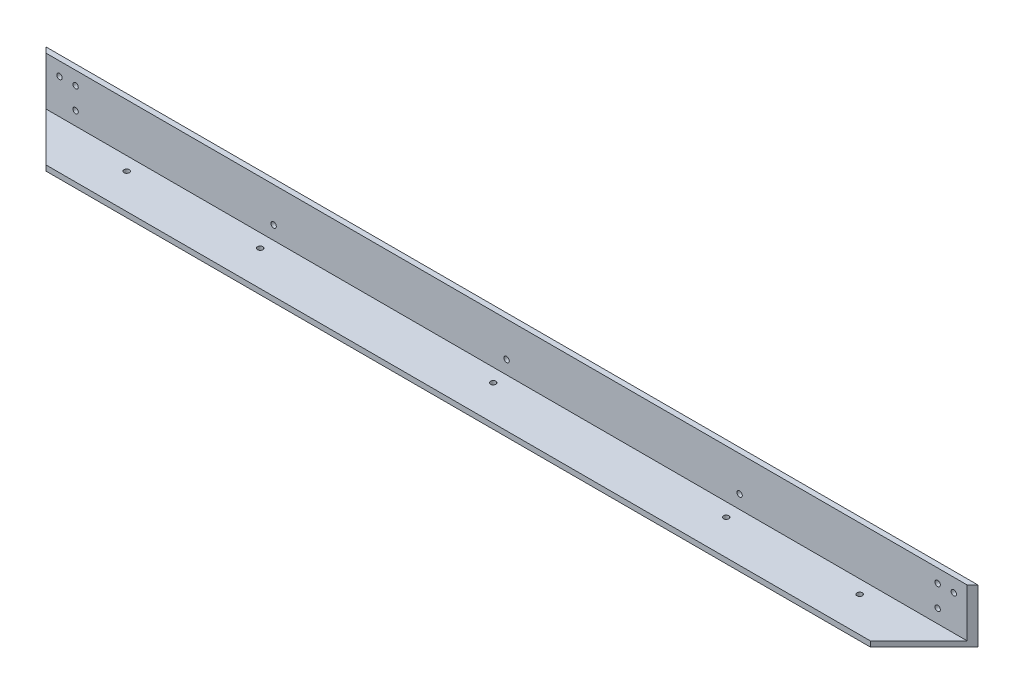
SolidWorks part; units mm, degrees
ref_plane "Front Plane" through (0, 0, 0) normal (0, 0, 1) x (1, 0, 0)
ref_plane "Top Plane" through (0, 0, 0) normal (0, 1, 0) x (1, 0, 0)
ref_plane "Right Plane" through (0, 0, 0) normal (1, 0, 0) x (0, 0, -1)
sketch "Sketch1" plane through (0, 0, 0) normal (1, 0, 0) x (0, 0, -1)
  line L0 (0, 0) -> (-31.75, 0)
  line L1 (-31.75, 0) -> (-31.75, 3.175)
  line L2 (-31.75, 3.175) -> (-3.175, 3.175)
  line L3 (-3.175, 3.175) -> (-3.175, 31.75)
  line L4 (-3.175, 31.75) -> (0, 31.75)
  line L5 (0, 31.75) -> (0, 0)
  dimension "LHeight" = 31.75
  dimension "LWidth" = 31.75
  dimension "LMaterialThickness" = 3.175
  dimension "D1" = 28.575
  dimension "D2" = 28.575
  dimension "D3" = 3.175
extrude "Boss-Extrude1" add sketch "Sketch1" along normal blind 550
chamfer "Chamfer6" distance 31.75 angle 45 1 edges at (550, 1.5875, 31.75)
chamfer "Chamfer7" distance 31.75 angle 45 1 edges at (0, 1.5875, 31.75)
sketch "TopHoles-Sketch3" plane through (0, 3.175, 0) normal (0, 1, 0) x (1, 0, 0)
  line L3 (550, 0) -> (0, 0) construction
  circle A9 centre (491.2625, -11.1125) radius 1.5875
  circle A10 centre (58.7375, -11.1125) radius 1.5875
  circle A13 centre (275, -11.1125) radius 1.5875
  circle A14 centre (137.5, -11.1125) radius 1.5875
  circle A15 centre (412.5, -11.1125) radius 1.5875
  point P8 (0, 0)
  point P9 (0, 0)
  point P11 (0, 0)
  point P12 (0, 0)
  point P20 (0, 0)
  point P21 (-1.5296, -23.0572)
  dimension "D8" = 137.5
  dimension "D10" = 137.5
  dimension "D5" = 3.175
  dimension "D11" = 137.5
  dimension "D2" = 11.1125
  dimension "D3" = 58.7375
  dimension "D4" = 58.7375
extrude "TopHoles-Cut-Extrude2" cut sketch "TopHoles-Sketch3" against normal through all
sketch "LeftHoles-Sketch4" plane through (0, 0, 3.175) normal (0, 0, 1) x (1, 0, 0)
  line L1 (550, 0) -> (0, 0) construction
  line L3 (550, 31.75) -> (0, 31.75) construction
  line L4 (0, 0) -> (0, 31.75) construction
  line L5 (550, 0) -> (550, 31.75) construction
  circle A1 centre (11.1125, 23.8125) radius 1.5875
  circle A3 centre (529.3625, 23.8125) radius 1.5875
  circle A4 centre (20.6375, 23.8125) radius 1.5875
  circle A5 centre (538.8875, 23.8125) radius 1.5875
  circle A7 centre (20.6375, 11.1125) radius 1.5875
  circle A8 centre (529.3625, 11.1125) radius 1.5875
  circle A10 centre (137.5, 11.1125) radius 1.5875
  circle A11 centre (275, 11.1125) radius 1.5875
  circle A12 centre (412.5, 11.1125) radius 1.5875
  dimension "D2" = 3.175
  dimension "D4" = 7.9375
  dimension "D1" = 11.1125
  dimension "D6" = 20.6375
  dimension "D3" = 11.1125
  dimension "D5" = 20.6375
  dimension "D8" = 137.5
  dimension "D9" = 137.5
  dimension "D10" = 137.5
  dimension "D7" = 11.1125
extrude "LeftHoles-Cut-Extrude3" cut sketch "LeftHoles-Sketch4" against normal through all
equation "\"TopRailWidth\"= 1.25in"
equation "\"TopRailHeight\"= 1.25in"
equation "\"RailThickness\"= .125in'Spec"
equation "\"SideRailHoleY1FromEdge\"= \"HoleOffsetFromEdge\""
equation "\"SideRailHoleX1FromSide\"= \"HoleOffsetFromSide\""
equation "\"SideRailLength\"= 550mm"
equation "\"VSWidth\"= 1.25in'Spec"
equation "\"HoleOffsetFromEdge\"= \"RailThickness\" * 2.5"
equation "\"HoleOffsetFromSide\"= \"RailThickness\" * 3.5"
equation "\"SideRailHoleX2FromSide\"= \"VSWidth\" - \"HoleOffsetFromEdge\" - \"RailThickness\"'Equals 20.6375"
equation "\"FasteningHoleDiameter\"= .125in"
equation "\"SideRailHoleY2FromSide\"= \"HoleOffsetFromSide\""
equation "\"D2@LeftHoles-Sketch4\"=\"FasteningHoleDiameter\""
equation "\"LWidth@Sketch1\"=\"TopRailWidth\""
equation "\"LHeight@Sketch1\"=\"TopRailHeight\""
equation "\"LMaterialThickness@Sketch1\"=\"RailThickness\""
equation "\"D1@Boss-Extrude1\"=\"SideRailLength\""
equation "\"D4@LeftHoles-Sketch4\"=\"SideRailHoleY1FromEdge\""
equation "\"D1@Chamfer6\"=\"TopRailWidth\""
equation "\"D1@Chamfer7\"=\"TopRailWidth\""
equation "\"D1@LeftHoles-Sketch4\"=\"SideRailHoleX1FromSide\""
equation "\"D6@LeftHoles-Sketch4\"=\"SideRailHoleX2FromSide\""
equation "\"D5@LeftHoles-Sketch4\"=\"SideRailHoleX2FromSide\""
equation "\"TopHoleY1FromSide\"= \"HoleOffsetFromSide\""
equation "\"TopCBLength\"= \"TopRailWidth\" * 2'Equals 63.5"
equation "\"LeftOrRightEnclosureHoleOffsets\"= \"SideRailLength\" / 4"
equation "\"D8@TopHoles-Sketch3\"=\"LeftOrRightEnclosureHoleOffsets\""
equation "\"D10@TopHoles-Sketch3\"=\"LeftOrRightEnclosureHoleOffsets\""
equation "\"D11@TopHoles-Sketch3\"=\"LeftOrRightEnclosureHoleOffsets\""
equation "\"D8@LeftHoles-Sketch4\"=\"LeftOrRightEnclosureHoleOffsets\""
equation "\"D9@LeftHoles-Sketch4\"=\"LeftOrRightEnclosureHoleOffsets\""
equation "\"D10@LeftHoles-Sketch4\"=\"LeftOrRightEnclosureHoleOffsets\""
equation "\"D7@LeftHoles-Sketch4\"=\"SideRailHoleY2FromSide\""
equation "\"LeftOrRightCornerEnclosureOffset\"= \"RailThickness\" + \"TopCBLength\" - \"HoleOffsetFromEdge\"'Equals 58.7375"
equation "\"D2@TopHoles-Sketch3\"=\"TopHoleY1FromSide\""
equation "\"D3@TopHoles-Sketch3\"=\"LeftOrRightCornerEnclosureOffset\""
equation "\"D4@TopHoles-Sketch3\"=\"LeftOrRightCornerEnclosureOffset\""
equation "\"D5@TopHoles-Sketch3\"=\"FasteningHoleDiameter\""
